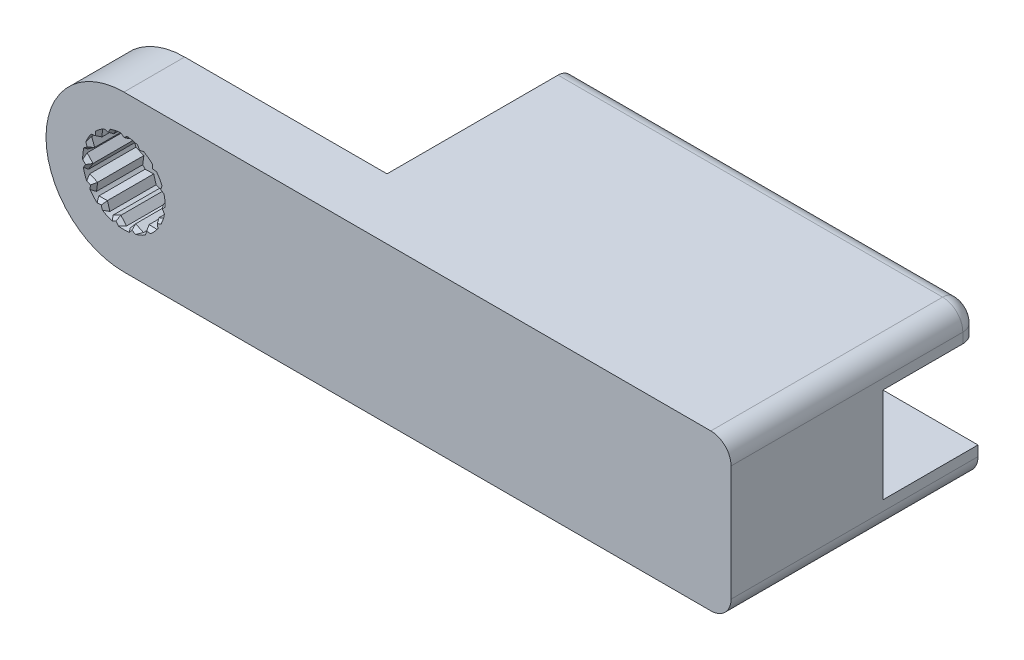
SolidWorks part; units mm, degrees
note: The reader was unsure of these and kept them because the rebuilt part matched: shared geometry of "Sketch1<4>", "Sketch1<5>", "Sketch1<6>", "Sketch1<7>".
ref_plane "Front Plane" through (0, 0, 0) normal (0, 0, 1) x (1, 0, 0)
ref_plane "Top Plane" through (0, 0, 0) normal (0, 1, 0) x (1, 0, 0)
ref_plane "Right Plane" through (0, 0, 0) normal (1, 0, 0) x (0, 0, -1)
sketch "Sketch1" plane through (0, 0, 0) normal (0, 0, 1) x (1, 0, 0)
  line L0 (0, 3.5) -> (-0.6731, 4.019)
  line L1 (0, 3.5) -> (0.6731, 4.019)
  line L2 (0, 7.7) -> (7.7, 7.7)
  line L3 (0, -7.7) -> (7.7, -7.7)
  line L4 (7.7, 7.7) -> (7.7, -7.7)
  line L5 (0, 0) -> (60, 0) construction
  line L6 (60, -4.7) -> (7.7, -4.7)
  line L7 (60, -4.7) -> (60, 4.7)
  line L8 (60, 4.7) -> (7.7, 4.7)
  line L9 (7.7, -4.7) -> (7.7, 4.7)
  line L10 (60, -4.7) -> (7.7, 4.7) construction
  line L11 (60, 4.7) -> (7.7, -4.7) construction
  line L12 (0, 0) -> (0, 9.7861) construction
  line L13 (20, 4.7) -> (60, 4.7)
  line L14 (20, 4.7) -> (20, 7.7)
  line L15 (20, 7.7) -> (60, 7.7)
  line L16 (60, 4.7) -> (60, 7.7)
  line L17 (20, 4.7) -> (20, -4.7)
  line L18 (30, -4.7) -> (60, -4.7)
  line L19 (30, -4.7) -> (30, -7.7)
  line L20 (30, -7.7) -> (60, -7.7)
  line L21 (60, -4.7) -> (60, -7.7)
  line L22 (7.7, 7.7) -> (20, 7.7)
  line L23 (7.7, -7.7) -> (30, -7.7)
  circle A0 centre (0, 0) radius 7.7
  circle A1 centre (0, 0) radius 4.075
  circle A2 centre (0, 0) radius 3.5 construction
  point P12 (33.85, 0)
  dimension "D1" = 8.15
  dimension "D2" = 7
  dimension "D3" = 15.4
  dimension "D4" = 0.85
  dimension "D5" = 9.4
  dimension "D6" = 20
  dimension "D7" = 40
  dimension "D8" = 3
  dimension "D9" = 3
  dimension "D10" = 30
  dimension "D11" = 30
extrude "outside" add sketch "Sketch1" along normal blind 5 contours A0 A1 | A0 L3 L4 L2 | A0 L3 L4 L9 | L7 L8 L4 L9 L6 | L8 L16 L15 L14 | L21 L6 L19 L20 | L17 L8 L4 L9 L6 | L22 L4 L8 L14 | L4 L23 L19 L6
extrude "single teeth" add sketch "Sketch1<4>" along normal blind 5 contours L1 A1 L0
sketch "Sketch1<4>" plane through (0, 0, 0) normal (0, 0, 1) x (1, 0, 0) same geometry as "Sketch1"
chamfer "teethChampfer" distance 0.25 angle 60 2 edges at (-0.3366, 3.7595, 5) (0.3366, 3.7595, 5)
pattern_circular "15th teeths" count 15 over 360 about axis through (0, 0, 0) along (0, 0, 1) of "single teeth", "teethChampfer"
extrude "cover" add sketch "Sketch1<5>" against normal blind 1 contours L0 A1 L1 | L1 A1 L0 | A0 A1 | A0 L3 L4 L2 | A0 L3 L4 L9 | L7 L8 L4 L9 L6 | L8 L16 L15 L14 | L21 L6 L19 L20 | L17 L8 L4 L9 L6 | L22 L4 L8 L14 | L4 L23 L19 L6
sketch "Sketch1<5>" plane through (0, 0, 0) normal (0, 0, 1) x (1, 0, 0) same geometry as "Sketch1"
extrude "gap filler" add sketch "Sketch1<6>" against normal blind 10 contours L8 L17 L6 L7
sketch "Sketch1<6>" plane through (0, 0, 0) normal (0, 0, 1) x (1, 0, 0) same geometry as "Sketch1"
extrude "holder" add sketch "Sketch1<7>" against normal blind 9.4 and the other way through all from vertex contours L8 L16 L15 L14 | L21 L6 L19 L20
sketch "Sketch1<7>" plane through (0, 0, 0) normal (0, 0, 1) x (1, 0, 0) same geometry as "Sketch1"
chamfer "reinfosment" distance 8 angle 20 1 edges at (30, -4.7, -5.5)
fillet "smooth" radius 2 2 edges at (60, -7.7, -7.2) (60, 7.7, -7.2)
fillet "zipTieSmoothing" radius 1.5 3 edges at (60, 5.2, -19.4) (59.4142, 7.1142, -19.4) (39, 7.7, -19.4)
equation "\"D9@Sketch1\"=\"D8@Sketch1\""
